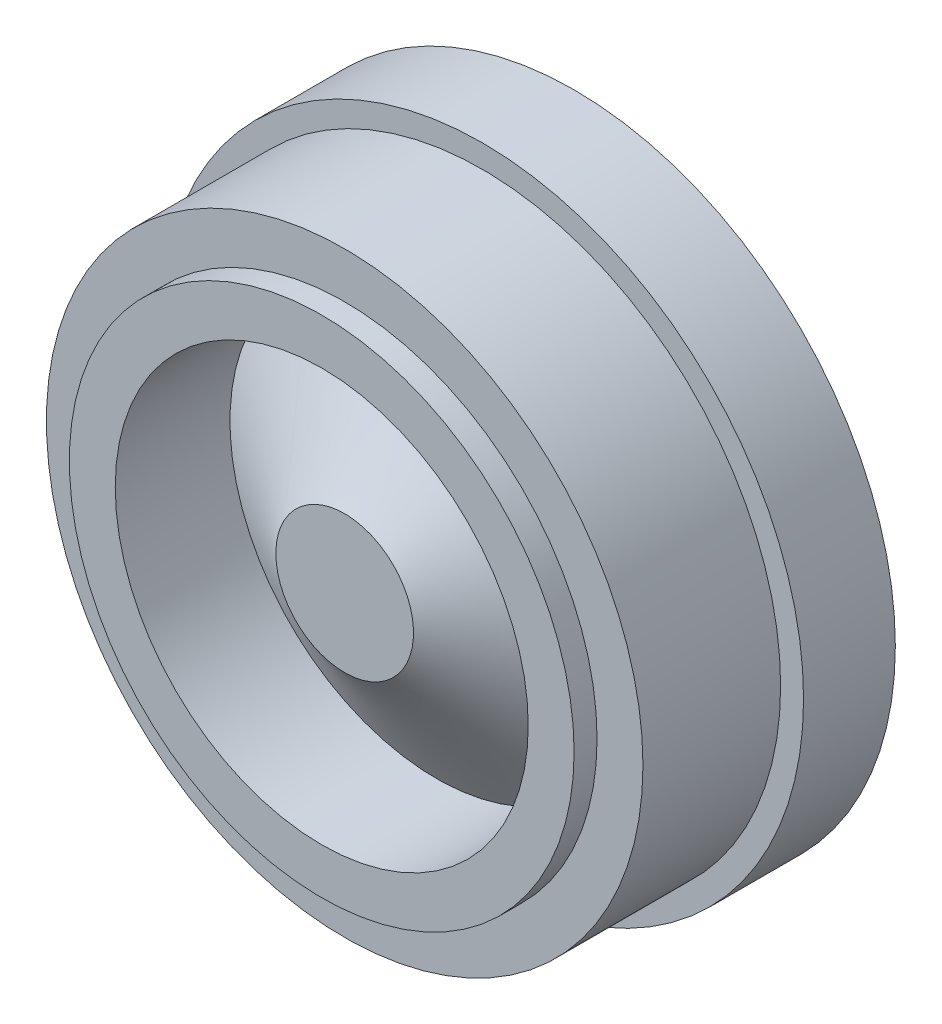
SolidWorks part; units mm, degrees
ref_plane "Front Plane" through (0, 0, 0) normal (0, 0, 1) x (1, 0, 0)
ref_plane "Top Plane" through (0, 0, 0) normal (0, 1, 0) x (1, 0, 0)
ref_plane "Right Plane" through (0, 0, 0) normal (1, 0, 0) x (0, 0, -1)
sketch "Sketch1" plane through (0, 0, 0) normal (0, 0, 1) x (1, 0, 0)
  circle A0 centre (0, 0) radius 14
  dimension "D1" = 28
extrude "Boss-Extrude1" add sketch "Sketch1" along normal blind 11
sketch "Sketch2" plane through (0, 0, 11) normal (0, 0, 1) x (1, 0, 0)
  circle A0 centre (0, 0) radius 13
  circle A1 centre (0, 0) radius 14
extrude "Cut-Extrude1" cut sketch "Sketch2" against normal blind 7
sketch "Sketch3" plane through (0, 0, 11) normal (0, 0, 1) x (1, 0, 0)
  circle A0 centre (0, 0) radius 11
  circle A1 centre (0, 0) radius 13
extrude "Cut-Extrude2" cut sketch "Sketch3" against normal blind 1
sketch "Sketch4" plane through (0, 0, 11) normal (0, 0, 1) x (1, 0, 0)
  circle A0 centre (0, 0) radius 9
extrude "Cut-Extrude3" cut sketch "Sketch4" against normal blind 5
sketch "Sketch5" plane through (0, 0, 0) normal (0, 0, -1) x (-1, 0, 0)
  circle A0 centre (0, 0) radius 5
extrude "Cut-Extrude4" cut sketch "Sketch5" against normal blind 5
sketch "Sketch6" plane through (0, 0, 6) normal (0, 0, 1) x (1, 0, 0)
  circle A0 centre (0, 0) radius 9
ref_plane "Plane1" through (0, 0, 10) normal (0, 0, 1) x (1, 0, 0)
sketch "Sketch7" plane through (0, 0, 10) normal (0, 0, 1) x (1, 0, 0)
  circle A0 centre (0, 0) radius 3
loft "Loft1" add profiles "Sketch7", "Sketch6" connector at (-2.6316, 1.4403, 10) connector at (-5.534, 7.0975, 6)
